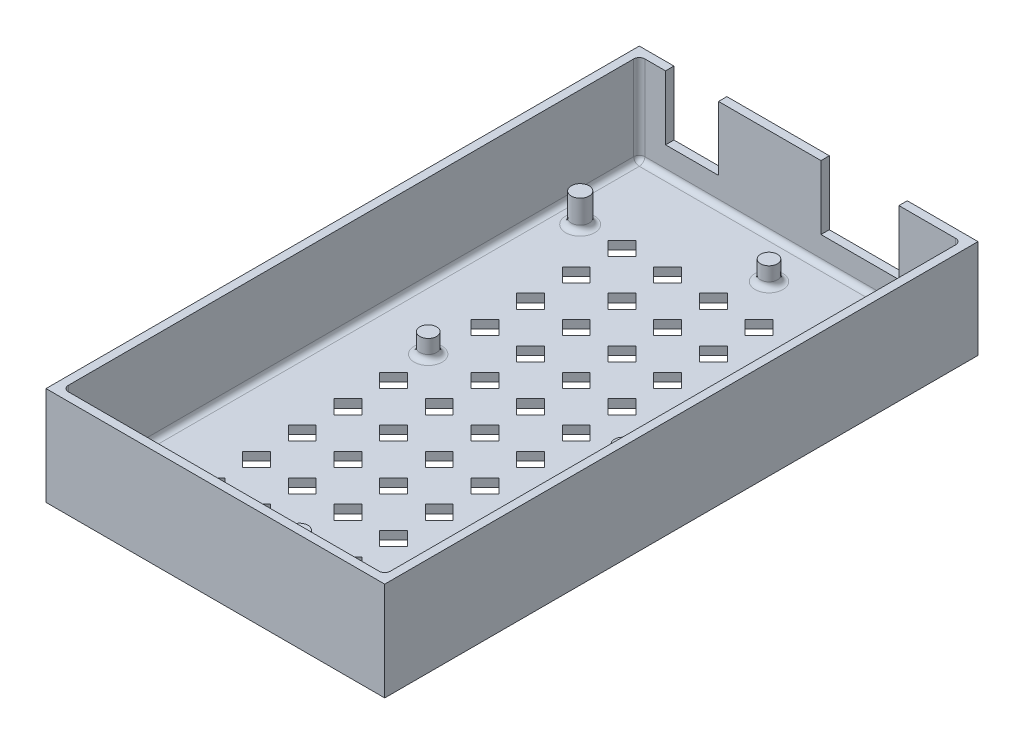
SolidWorks part; units mm, degrees
ref_plane "Front Plane" through (0, 0, 0) normal (0, 0, 1) x (1, 0, 0)
ref_plane "Top Plane" through (0, 0, 0) normal (0, 1, 0) x (1, 0, 0)
ref_plane "Right Plane" through (0, 0, 0) normal (1, 0, 0) x (0, 0, -1)
sketch "Sketch1" plane through (0, 0, 0) normal (0, 1, 0) x (1, 0, 0)
  line L0 (24.55, 14.33) -> (24.55, 20.83) construction
  line L1 (3.0629, 20.83) -> (15.05, 20.83) construction
  line L2 (-2.2, -87.17) -> (-2.2, -88.17) construction
  line L3 (24.55, 14.33) -> (15.05, 14.33) construction
  line L4 (24.55, 14.33) -> (-1.7, 14.33) construction
  line L5 (24.55, 14.33) -> (24.55, -87.17) construction
  line L6 (24.55, -87.17) -> (-28.95, -87.17) construction
  line L7 (-28.95, -87.17) -> (-28.95, 14.33) construction
  line L8 (-28.95, 14.33) -> (-1.7, 14.33) construction
  line L9 (15.05, 14.33) -> (15.05, 20.83) construction
  line L10 (3.0629, 14.0695) -> (3.0629, 20.83) construction
  line L11 (-2.2, -88.17) -> (27.25, -88.17)
  line L12 (27.25, -88.17) -> (27.25, 15.33)
  line L13 (-2.2, -88.17) -> (-30.55, -88.17)
  line L14 (-30.55, -88.17) -> (-30.55, 15.33)
  line L15 (-30.55, 15.33) -> (27.25, 15.33)
  line L16 (-2.2, -88.17) -> (-2.2, -89.67) construction
  line L17 (-2.2, -89.67) -> (-32.05, -89.67)
  line L18 (-2.2, -89.67) -> (28.75, -89.67)
  line L19 (28.75, -89.67) -> (28.75, 16.83)
  line L20 (-32.05, -89.67) -> (-32.05, 16.83)
  line L21 (-32.05, 16.83) -> (28.75, 16.83)
  circle A0 centre (22.43, -1.27) radius 1.6
  circle A1 centre (-25.83, 0) radius 1.6
  circle A2 centre (22.43, -76.2) radius 1.6
  circle A3 centre (-25.83, -82.55) radius 1.6
  dimension "D5" = 3.2
  dimension "D6" = 3.2
  dimension "D7" = 3.2
  dimension "D9" = 3.2
  dimension "D1" = 48.26
  dimension "D2" = 48.26
  dimension "D3" = 15.6
  dimension "D4" = 74.93
  dimension "D8" = 82.55
  dimension "D10" = 6.5
  dimension "D11" = 101.5
  dimension "D12" = 53.5
  dimension "D13" = 1
  dimension "D14" = 9.5
  dimension "D15" = 29.45
  dimension "D16" = 103.5
  dimension "D17" = 28.35
  dimension "D18" = 1.5
  dimension "D19" = 29.85
  dimension "D20" = 30.95
  dimension "D21" = 106.5
  dimension "D22" = 26.75
extrude "Boss-Extrude1" add sketch "Sketch1" against normal blind 1.5 from offset 3.5 contours L21 L20 L17 L18 L19 L14 L15 L12 L11 L13 | L15 L14 L13 L11 L12 A3 A2 A1 A0 | A3 | A1 | A0 | A2 region at (-1.6497, 0, 36.4006) region at (-17.125, 0, 88.4437) offset against normal yes
extrude "Boss-Extrude2" add sketch "Sketch1<3>" along normal blind 3.5 from offset 3.5 separate body contours L21 L20 L17 L18 L19 L14 L15 L12 L11 L13 region at (-17.125, 0, 88.4437) offset against normal yes
sketch "Sketch1<3>" plane through (0, 0, 0) normal (0, 1, 0) x (1, 0, 0) same geometry as "Sketch1"
extrude "Boss-Extrude3" add sketch "Sketch1<5>" along normal blind 1.7 contours L21 L20 L17 L18 L19 L14 L15 L12 L11 L13 region at (-17.125, 0, 88.4437)
sketch "Sketch1<5>" plane through (0, 0, 0) normal (0, 1, 0) x (1, 0, 0) same geometry as "Sketch1"
sketch "Sketch2" plane through (0, -3.5, 0) normal (0, 1, 0) x (1, 0, 0)
  line L0 (0, 0) -> (0, -91.3462) construction
  line L1 (22.43, -76.2) -> (-5.5383, -76.2) construction
  line L2 (-46.2052, -33.8148) -> (51.2971, -33.8148) construction
  line L3 (0, 0) -> (0, 21.5785) construction
  circle A0 centre (0, -76.2) radius 1.5
  circle A1 centre (-19.297, -33.8148) radius 1.5
  circle A2 centre (15.644, -33.8148) radius 1.5
  circle A3 centre (0, 8.0639) radius 1.5
  dimension "D1" = 3
  dimension "D2" = 3
  dimension "D3" = 3
  dimension "D4" = 3
extrude "Boss-Extrude4" add sketch "Sketch2" along normal blind 3.5
extrude "Boss-Extrude5" add sketch "Sketch1<7>" along normal blind 5.2 from offset 3.5 contours A1 | A0 | A3 | A2 region at (22.43, 0, 1.27) region at (-25.83, 0, 0) region at (-25.83, 0, 82.55) offset against normal yes
sketch "Sketch1<7>" plane through (0, 0, 0) normal (0, 1, 0) x (1, 0, 0) same geometry as "Sketch1"
fillet "Fillet5" radius 1 12 edges at (27.25, -3.5, 36.42) (-1.65, -3.5, 88.17) (-30.55, -3.5, 36.42) (-1.65, -3.5, -15.33) (0, -3.5, 77.7) (-19.297, -3.5, 35.3148) (15.644, -3.5, 35.3148) (0, -3.5, -6.5639) (-25.83, -3.5, 1.6) (22.43, -3.5, 2.87) (-25.83, -3.5, 84.15) (22.43, -3.5, 77.8)
sketch "Sketch3" plane through (0, 1.7, 0) normal (0, 1, 0) x (1, 0, 0)
  line L0 (0, 0) -> (0, 25.6693) construction
  line L1 (-25.83, 16.83) -> (-32.05, 16.83)
  line L2 (-32.05, 16.83) -> (28.75, 16.83) construction
  line L3 (2.0636, 16.83) -> (2.0636, 15.33)
  line L4 (-30.55, 15.33) -> (27.25, 15.33) construction
  line L5 (-25.83, 0) -> (-25.83, 21.0788) construction
  line L6 (-32.05, 16.83) -> (-32.05, -89.67)
  line L7 (-32.05, -89.67) -> (28.75, -89.67)
  line L8 (-30.55, 15.33) -> (27.25, 15.33) construction
  line L9 (16.0551, 16.83) -> (16.0551, 15.33)
  line L10 (-16.33, 16.83) -> (2.0636, 16.83)
  line L11 (-16.33, 16.83) -> (-16.33, 15.33)
  line L12 (-25.83, 16.83) -> (-25.83, 15.33)
  line L13 (28.75, -89.67) -> (28.75, 16.83)
  line L14 (28.75, 16.83) -> (16.0551, 16.83)
  line L15 (-16.33, 15.33) -> (2.0636, 15.33)
  line L16 (16.0551, 15.33) -> (27.25, 15.33)
  line L17 (27.25, 15.33) -> (27.25, -88.17)
  line L18 (27.25, -88.17) -> (-30.55, -88.17)
  line L19 (-30.55, -88.17) -> (-30.55, 15.33)
  line L20 (-30.55, 15.33) -> (-25.83, 15.33)
  dimension "D4" = 9.5
extrude "Boss-Extrude6" add sketch "Sketch3" along normal blind 11
sketch "Sketch4" plane through (0, 0, -16.83) normal (0, 0, -1) x (-1, 0, 0)
  line L0 (-16.0551, 1.7) -> (-16.0551, 1.2)
  line L1 (-16.0551, 1.7) -> (-2.0636, 1.7)
  line L2 (-2.0636, 1.7) -> (-2.0636, 1.2)
  line L3 (-2.0636, 1.2) -> (-16.0551, 1.2)
  line L4 (16.33, 1.7) -> (16.33, 1.2)
  line L5 (16.33, 1.7) -> (25.83, 1.7)
  line L6 (25.83, 1.7) -> (25.83, 1.2)
  line L7 (25.83, 1.2) -> (16.33, 1.2)
  dimension "D1" = 0.5
  dimension "D2" = 0.5
extrude "Cut-Extrude1" cut sketch "Sketch4" against normal blind 11
fillet "Fillet6" radius 1 8 edges at (-30.2571, -3.2071, -15.0371) (26.9571, -3.2071, -15.0371) (26.9571, -3.2071, 87.8771) (-30.2571, -3.2071, 87.8771) (-30.55, 5.1, -15.33) (27.25, 5.1, -15.33) (27.25, 5.1, 88.17) (-30.55, 5.1, 88.17)
sketch "Sketch5" plane through (0, -3.5, 0) normal (0, 1, 0) x (1, 0, 0)
  line L0 (-25.83, 0) -> (38.3375, 0) construction
  line L1 (0, 14.33) -> (0, -99.4929) construction
  line L2 (26.25, 14.33) -> (-29.55, 14.33) construction
  line L3 (-12.63, 0) -> (-10.13, 2.5)
  line L4 (-20.83, 0) -> (-18.33, 0) construction
  line L5 (-18.33, 0) -> (-18.33, 2.5) construction
  line L6 (-20.83, 0) -> (-18.33, 2.5)
  line L7 (-18.33, 2.5) -> (-15.83, 0)
  line L8 (-15.83, 0) -> (-18.33, -2.5)
  line L9 (-18.33, -2.5) -> (-20.83, 0)
  line L10 (-10.13, 2.5) -> (-7.63, 0)
  line L11 (-7.63, 0) -> (-10.13, -2.5)
  line L12 (-10.13, -2.5) -> (-12.63, 0)
  line L13 (-12.63, 0) -> (-10.13, 0) construction
  line L14 (-10.13, 0) -> (-10.13, 2.5) construction
  line L15 (-4.43, 0) -> (-1.93, 2.5)
  line L16 (-1.93, 2.5) -> (0.57, 0)
  line L17 (0.57, 0) -> (-1.93, -2.5)
  line L18 (-1.93, -2.5) -> (-4.43, 0)
  line L19 (-4.43, 0) -> (-1.93, 0) construction
  line L20 (-1.93, 0) -> (-1.93, 2.5) construction
  line L21 (3.77, 0) -> (6.27, 2.5)
  line L22 (6.27, 2.5) -> (8.77, 0)
  line L23 (8.77, 0) -> (6.27, -2.5)
  line L24 (6.27, -2.5) -> (3.77, 0)
  line L25 (3.77, 0) -> (6.27, 0) construction
  line L26 (6.27, 0) -> (6.27, 2.5) construction
  line L27 (11.97, 0) -> (14.47, 2.5)
  line L28 (14.47, 2.5) -> (16.97, 0)
  line L29 (16.97, 0) -> (14.47, -2.5)
  line L30 (14.47, -2.5) -> (11.97, 0)
  line L31 (11.97, 0) -> (14.47, 0) construction
  line L32 (14.47, 0) -> (14.47, 2.5) construction
  line L33 (-12.63, -8.2) -> (-10.13, -5.7)
  line L34 (-10.13, -5.7) -> (-7.63, -8.2)
  line L35 (-7.63, -8.2) -> (-10.13, -10.7)
  line L36 (-10.13, -10.7) -> (-12.63, -8.2)
  line L37 (-12.63, -8.2) -> (-10.13, -8.2) construction
  line L38 (-10.13, -8.2) -> (-10.13, -5.7) construction
  line L39 (-4.43, -8.2) -> (-1.93, -5.7)
  line L40 (-1.93, -5.7) -> (0.57, -8.2)
  line L41 (0.57, -8.2) -> (-1.93, -10.7)
  line L42 (-1.93, -10.7) -> (-4.43, -8.2)
  line L43 (-4.43, -8.2) -> (-1.93, -8.2) construction
  line L44 (-1.93, -8.2) -> (-1.93, -5.7) construction
  line L45 (3.77, -8.2) -> (6.27, -5.7)
  line L46 (6.27, -5.7) -> (8.77, -8.2)
  line L47 (8.77, -8.2) -> (6.27, -10.7)
  line L48 (6.27, -10.7) -> (3.77, -8.2)
  line L49 (3.77, -8.2) -> (6.27, -8.2) construction
  line L50 (6.27, -8.2) -> (6.27, -5.7) construction
  line L51 (11.97, -8.2) -> (14.47, -5.7)
  line L52 (14.47, -5.7) -> (16.97, -8.2)
  line L53 (16.97, -8.2) -> (14.47, -10.7)
  line L54 (14.47, -10.7) -> (11.97, -8.2)
  line L55 (11.97, -8.2) -> (14.47, -8.2) construction
  line L56 (14.47, -8.2) -> (14.47, -5.7) construction
  line L57 (-12.63, -16.4) -> (-10.13, -13.9)
  line L58 (-10.13, -13.9) -> (-7.63, -16.4)
  line L59 (-7.63, -16.4) -> (-10.13, -18.9)
  line L60 (-10.13, -18.9) -> (-12.63, -16.4)
  line L61 (-12.63, -16.4) -> (-10.13, -16.4) construction
  line L62 (-10.13, -16.4) -> (-10.13, -13.9) construction
  line L63 (-4.43, -16.4) -> (-1.93, -13.9)
  line L64 (-1.93, -13.9) -> (0.57, -16.4)
  line L65 (0.57, -16.4) -> (-1.93, -18.9)
  line L66 (-1.93, -18.9) -> (-4.43, -16.4)
  line L67 (-4.43, -16.4) -> (-1.93, -16.4) construction
  line L68 (-1.93, -16.4) -> (-1.93, -13.9) construction
  line L69 (3.77, -16.4) -> (6.27, -13.9)
  line L70 (6.27, -13.9) -> (8.77, -16.4)
  line L71 (8.77, -16.4) -> (6.27, -18.9)
  line L72 (6.27, -18.9) -> (3.77, -16.4)
  line L73 (3.77, -16.4) -> (6.27, -16.4) construction
  line L74 (6.27, -16.4) -> (6.27, -13.9) construction
  line L75 (11.97, -16.4) -> (14.47, -13.9)
  line L76 (14.47, -13.9) -> (16.97, -16.4)
  line L77 (16.97, -16.4) -> (14.47, -18.9)
  line L78 (14.47, -18.9) -> (11.97, -16.4)
  line L79 (11.97, -16.4) -> (14.47, -16.4) construction
  line L80 (14.47, -16.4) -> (14.47, -13.9) construction
  line L81 (-12.63, -24.6) -> (-10.13, -22.1)
  line L82 (-10.13, -22.1) -> (-7.63, -24.6)
  line L83 (-7.63, -24.6) -> (-10.13, -27.1)
  line L84 (-10.13, -27.1) -> (-12.63, -24.6)
  line L85 (-12.63, -24.6) -> (-10.13, -24.6) construction
  line L86 (-10.13, -24.6) -> (-10.13, -22.1) construction
  line L87 (-4.43, -24.6) -> (-1.93, -22.1)
  line L88 (-1.93, -22.1) -> (0.57, -24.6)
  line L89 (0.57, -24.6) -> (-1.93, -27.1)
  line L90 (-1.93, -27.1) -> (-4.43, -24.6)
  line L91 (-4.43, -24.6) -> (-1.93, -24.6) construction
  line L92 (-1.93, -24.6) -> (-1.93, -22.1) construction
  line L93 (3.77, -24.6) -> (6.27, -22.1)
  line L94 (6.27, -22.1) -> (8.77, -24.6)
  line L95 (8.77, -24.6) -> (6.27, -27.1)
  line L96 (6.27, -27.1) -> (3.77, -24.6)
  line L97 (3.77, -24.6) -> (6.27, -24.6) construction
  line L98 (6.27, -24.6) -> (6.27, -22.1) construction
  line L99 (11.97, -24.6) -> (14.47, -22.1)
  line L100 (14.47, -22.1) -> (16.97, -24.6)
  line L101 (16.97, -24.6) -> (14.47, -27.1)
  line L102 (14.47, -27.1) -> (11.97, -24.6)
  line L103 (11.97, -24.6) -> (14.47, -24.6) construction
  line L104 (14.47, -24.6) -> (14.47, -22.1) construction
  line L105 (-20.83, -8.2) -> (-18.33, -5.7)
  line L106 (-18.33, -5.7) -> (-15.83, -8.2)
  line L107 (-15.83, -8.2) -> (-18.33, -10.7)
  line L108 (-18.33, -10.7) -> (-20.83, -8.2)
  line L109 (-20.83, -8.2) -> (-18.33, -8.2) construction
  line L110 (-18.33, -8.2) -> (-18.33, -5.7) construction
  line L111 (-20.83, -16.4) -> (-18.33, -13.9)
  line L112 (-18.33, -13.9) -> (-15.83, -16.4)
  line L113 (-15.83, -16.4) -> (-18.33, -18.9)
  line L114 (-18.33, -18.9) -> (-20.83, -16.4)
  line L115 (-20.83, -16.4) -> (-18.33, -16.4) construction
  line L116 (-18.33, -16.4) -> (-18.33, -13.9) construction
  line L117 (-20.83, -24.6) -> (-18.33, -22.1)
  line L118 (-18.33, -22.1) -> (-15.83, -24.6)
  line L119 (-15.83, -24.6) -> (-18.33, -27.1)
  line L120 (-18.33, -27.1) -> (-20.83, -24.6)
  line L121 (-20.83, -24.6) -> (-18.33, -24.6) construction
  line L122 (-18.33, -24.6) -> (-18.33, -22.1) construction
  line L123 (-1.93, -24.6) -> (-1.93, -28.7) construction
  line L124 (-19.1242, -28.7) -> (18.4628, -28.7) construction
  line L125 (6.27, -32.8) -> (6.27, -35.3) construction
  line L126 (3.77, -32.8) -> (6.27, -32.8) construction
  line L127 (-1.93, -32.8) -> (-1.93, -35.3) construction
  line L128 (-4.43, -32.8) -> (-1.93, -32.8) construction
  line L129 (-10.13, -32.8) -> (-10.13, -35.3) construction
  line L130 (-12.63, -32.8) -> (-10.13, -32.8) construction
  line L131 (6.27, -30.3) -> (3.77, -32.8)
  line L132 (8.77, -32.8) -> (6.27, -30.3)
  line L133 (6.27, -35.3) -> (8.77, -32.8)
  line L134 (3.77, -32.8) -> (6.27, -35.3)
  line L135 (-1.93, -30.3) -> (-4.43, -32.8)
  line L136 (0.57, -32.8) -> (-1.93, -30.3)
  line L137 (-1.93, -35.3) -> (0.57, -32.8)
  line L138 (-4.43, -32.8) -> (-1.93, -35.3)
  line L139 (-10.13, -30.3) -> (-12.63, -32.8)
  line L140 (-7.63, -32.8) -> (-10.13, -30.3)
  line L141 (-10.13, -35.3) -> (-7.63, -32.8)
  line L142 (-12.63, -32.8) -> (-10.13, -35.3)
  line L143 (-18.33, -41) -> (-18.33, -43.5) construction
  line L144 (-20.83, -41) -> (-18.33, -41) construction
  line L145 (-18.33, -49.2) -> (-18.33, -51.7) construction
  line L146 (-20.83, -49.2) -> (-18.33, -49.2) construction
  line L147 (14.47, -41) -> (14.47, -43.5) construction
  line L148 (11.97, -41) -> (14.47, -41) construction
  line L149 (6.27, -41) -> (6.27, -43.5) construction
  line L150 (3.77, -41) -> (6.27, -41) construction
  line L151 (-1.93, -41) -> (-1.93, -43.5) construction
  line L152 (-4.43, -41) -> (-1.93, -41) construction
  line L153 (-10.13, -41) -> (-10.13, -43.5) construction
  line L154 (-12.63, -41) -> (-10.13, -41) construction
  line L155 (14.47, -49.2) -> (14.47, -51.7) construction
  line L156 (11.97, -49.2) -> (14.47, -49.2) construction
  line L157 (6.27, -49.2) -> (6.27, -51.7) construction
  line L158 (3.77, -49.2) -> (6.27, -49.2) construction
  line L159 (-1.93, -49.2) -> (-1.93, -51.7) construction
  line L160 (-4.43, -49.2) -> (-1.93, -49.2) construction
  line L161 (-10.13, -49.2) -> (-10.13, -51.7) construction
  line L162 (-12.63, -49.2) -> (-10.13, -49.2) construction
  line L163 (14.47, -57.4) -> (14.47, -59.9) construction
  line L164 (11.97, -57.4) -> (14.47, -57.4) construction
  line L165 (6.27, -57.4) -> (6.27, -59.9) construction
  line L166 (3.77, -57.4) -> (6.27, -57.4) construction
  line L167 (-1.93, -57.4) -> (-1.93, -59.9) construction
  line L168 (-4.43, -57.4) -> (-1.93, -57.4) construction
  line L169 (-10.13, -57.4) -> (-10.13, -59.9) construction
  line L170 (-12.63, -57.4) -> (-10.13, -57.4) construction
  line L171 (-18.33, -57.4) -> (-18.33, -59.9) construction
  line L172 (-20.83, -57.4) -> (-18.33, -57.4) construction
  line L173 (0, -71.73) -> (0, 42.0929) construction
  line L174 (-25.83, -57.4) -> (38.3375, -57.4) construction
  line L175 (-18.33, -38.5) -> (-20.83, -41)
  line L176 (-15.83, -41) -> (-18.33, -38.5)
  line L177 (-18.33, -43.5) -> (-15.83, -41)
  line L178 (-20.83, -41) -> (-18.33, -43.5)
  line L179 (-18.33, -46.7) -> (-20.83, -49.2)
  line L180 (-15.83, -49.2) -> (-18.33, -46.7)
  line L181 (-18.33, -51.7) -> (-15.83, -49.2)
  line L182 (-20.83, -49.2) -> (-18.33, -51.7)
  line L183 (14.47, -38.5) -> (11.97, -41)
  line L184 (16.97, -41) -> (14.47, -38.5)
  line L185 (14.47, -43.5) -> (16.97, -41)
  line L186 (11.97, -41) -> (14.47, -43.5)
  line L187 (6.27, -38.5) -> (3.77, -41)
  line L188 (8.77, -41) -> (6.27, -38.5)
  line L189 (6.27, -43.5) -> (8.77, -41)
  line L190 (3.77, -41) -> (6.27, -43.5)
  line L191 (-1.93, -38.5) -> (-4.43, -41)
  line L192 (0.57, -41) -> (-1.93, -38.5)
  line L193 (-1.93, -43.5) -> (0.57, -41)
  line L194 (-4.43, -41) -> (-1.93, -43.5)
  line L195 (-10.13, -38.5) -> (-12.63, -41)
  line L196 (-7.63, -41) -> (-10.13, -38.5)
  line L197 (-10.13, -43.5) -> (-7.63, -41)
  line L198 (-12.63, -41) -> (-10.13, -43.5)
  line L199 (14.47, -46.7) -> (11.97, -49.2)
  line L200 (16.97, -49.2) -> (14.47, -46.7)
  line L201 (14.47, -51.7) -> (16.97, -49.2)
  line L202 (11.97, -49.2) -> (14.47, -51.7)
  line L203 (6.27, -46.7) -> (3.77, -49.2)
  line L204 (8.77, -49.2) -> (6.27, -46.7)
  line L205 (6.27, -51.7) -> (8.77, -49.2)
  line L206 (3.77, -49.2) -> (6.27, -51.7)
  line L207 (-1.93, -46.7) -> (-4.43, -49.2)
  line L208 (0.57, -49.2) -> (-1.93, -46.7)
  line L209 (-1.93, -51.7) -> (0.57, -49.2)
  line L210 (-4.43, -49.2) -> (-1.93, -51.7)
  line L211 (-10.13, -46.7) -> (-12.63, -49.2)
  line L212 (-7.63, -49.2) -> (-10.13, -46.7)
  line L213 (-10.13, -51.7) -> (-7.63, -49.2)
  line L214 (-12.63, -49.2) -> (-10.13, -51.7)
  line L215 (14.47, -54.9) -> (11.97, -57.4)
  line L216 (16.97, -57.4) -> (14.47, -54.9)
  line L217 (14.47, -59.9) -> (16.97, -57.4)
  line L218 (11.97, -57.4) -> (14.47, -59.9)
  line L219 (6.27, -54.9) -> (3.77, -57.4)
  line L220 (8.77, -57.4) -> (6.27, -54.9)
  line L221 (6.27, -59.9) -> (8.77, -57.4)
  line L222 (3.77, -57.4) -> (6.27, -59.9)
  line L223 (-1.93, -54.9) -> (-4.43, -57.4)
  line L224 (0.57, -57.4) -> (-1.93, -54.9)
  line L225 (-1.93, -59.9) -> (0.57, -57.4)
  line L226 (-4.43, -57.4) -> (-1.93, -59.9)
  line L227 (-10.13, -54.9) -> (-12.63, -57.4)
  line L228 (-7.63, -57.4) -> (-10.13, -54.9)
  line L229 (-10.13, -59.9) -> (-7.63, -57.4)
  line L230 (-18.33, -54.9) -> (-20.83, -57.4)
  line L231 (-15.83, -57.4) -> (-18.33, -54.9)
  line L232 (-18.33, -59.9) -> (-15.83, -57.4)
  line L233 (-20.83, -57.4) -> (-18.33, -59.9)
  line L234 (-12.63, -57.4) -> (-10.13, -59.9)
  line L235 (0, -43.07) -> (0, -156.8929) construction
  line L236 (-12.63, -65.6) -> (-10.13, -65.6) construction
  line L237 (-10.13, -65.6) -> (-10.13, -63.1) construction
  line L238 (-4.43, -65.6) -> (-1.93, -65.6) construction
  line L239 (-1.93, -65.6) -> (-1.93, -63.1) construction
  line L240 (3.77, -65.6) -> (6.27, -65.6) construction
  line L241 (6.27, -65.6) -> (6.27, -63.1) construction
  line L242 (11.97, -65.6) -> (14.47, -65.6) construction
  line L243 (14.47, -65.6) -> (14.47, -63.1) construction
  line L244 (-20.83, -65.6) -> (-18.33, -65.6) construction
  line L245 (-18.33, -65.6) -> (-18.33, -63.1) construction
  line L246 (0, -129.13) -> (0, -15.3071) construction
  line L247 (-12.63, -65.6) -> (-10.13, -63.1)
  line L248 (-10.13, -63.1) -> (-7.63, -65.6)
  line L249 (-7.63, -65.6) -> (-10.13, -68.1)
  line L250 (-10.13, -68.1) -> (-12.63, -65.6)
  line L251 (-4.43, -65.6) -> (-1.93, -63.1)
  line L252 (-1.93, -63.1) -> (0.57, -65.6)
  line L253 (0.57, -65.6) -> (-1.93, -68.1)
  line L254 (-1.93, -68.1) -> (-4.43, -65.6)
  line L255 (3.77, -65.6) -> (6.27, -63.1)
  line L256 (6.27, -63.1) -> (8.77, -65.6)
  line L257 (8.77, -65.6) -> (6.27, -68.1)
  line L258 (6.27, -68.1) -> (3.77, -65.6)
  line L259 (11.97, -65.6) -> (14.47, -63.1)
  line L260 (14.47, -63.1) -> (16.97, -65.6)
  line L261 (16.97, -65.6) -> (14.47, -68.1)
  line L262 (14.47, -68.1) -> (11.97, -65.6)
  line L263 (-20.83, -65.6) -> (-18.33, -63.1)
  line L264 (-18.33, -63.1) -> (-15.83, -65.6)
  line L265 (-15.83, -65.6) -> (-18.33, -68.1)
  line L266 (-18.33, -68.1) -> (-20.83, -65.6)
  line L267 (-12.63, -73.8) -> (-10.13, -73.8) construction
  line L268 (-10.13, -73.8) -> (-10.13, -71.3) construction
  line L269 (-20.83, -73.8) -> (-18.33, -73.8) construction
  line L270 (-18.33, -73.8) -> (-18.33, -71.3) construction
  line L271 (-12.63, -73.8) -> (-10.13, -71.3)
  line L272 (-10.13, -71.3) -> (-7.63, -73.8)
  line L273 (-7.63, -73.8) -> (-10.13, -76.3)
  line L274 (-10.13, -76.3) -> (-12.63, -73.8)
  line L275 (-20.83, -73.8) -> (-18.33, -71.3)
  line L276 (-18.33, -71.3) -> (-15.83, -73.8)
  line L277 (-15.83, -73.8) -> (-18.33, -76.3)
  line L278 (-18.33, -76.3) -> (-20.83, -73.8)
  line L279 (3.77, -73.8) -> (6.27, -73.8) construction
  line L280 (6.27, -73.8) -> (6.27, -71.3) construction
  line L281 (11.97, -73.8) -> (14.47, -73.8) construction
  line L282 (14.47, -73.8) -> (14.47, -71.3) construction
  line L283 (3.77, -73.8) -> (6.27, -71.3)
  line L284 (6.27, -71.3) -> (8.77, -73.8)
  line L285 (8.77, -73.8) -> (6.27, -76.3)
  line L286 (6.27, -76.3) -> (3.77, -73.8)
  line L287 (11.97, -73.8) -> (14.47, -71.3)
  line L288 (14.47, -71.3) -> (16.97, -73.8)
  line L289 (16.97, -73.8) -> (14.47, -76.3)
  line L290 (14.47, -76.3) -> (11.97, -73.8)
  dimension "D1" = 5
  dimension "D2" = 2.5
  dimension "D3" = 2.5
  dimension "D6" = 4.1
  dimension "D4" = 5
  dimension "D5" = 4
extrude "Cut-Extrude2" cut sketch "Sketch5" against normal through all
